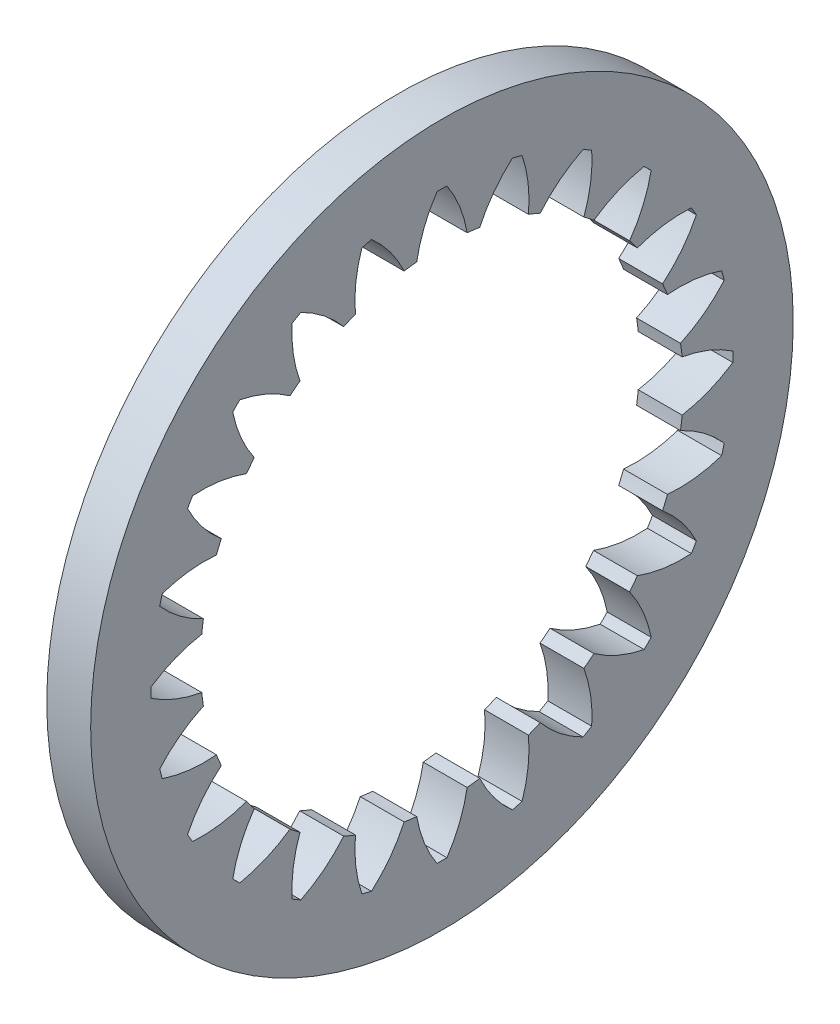
SolidWorks part; units mm, degrees
ref_plane "Plane1" through (0, 0, 0) normal (0, 0, 1) x (1, 0, 0)
ref_plane "Plane2" through (0, 0, 0) normal (0, 1, 0) x (1, 0, 0)
ref_plane "Plane3" through (0, 0, 0) normal (1, 0, 0) x (0, 0, -1)
sketch "HoldingSke" plane through (0, 0, 0) normal (0, 1, 0) x (1, 0, 0)
  line L0 (0, 0) -> (-17.6427, -100.0565)
  line L1 (-15, 0) -> (100, 0) construction
  line L2 (0, 0) -> (-2.1039, 2.3779)
  line L3 (0, 0) -> (-11.863, 4.5341)
  line L4 (0, 0) -> (7.8894, 3.5126)
  line L5 (0, 0) -> (-23.7986, -8.8762)
  line L6 (0, 0) -> (-10.5278, -7.1032)
  line L7 (-2.1039, 2.3779) -> (3.3635, 27.1825)
  line L8 (-76.2, 54.61) -> (-54.61, 54.61)
  line L9 (-67.7845, 28.3722) -> (-49.3413, 33.142)
  line L10 (-76.2, 71.12) -> (104.1128, 71.12)
  line L11 (0, 0) -> (-12.7, 0)
  line L12 (-76.2, 101.6) -> (-75.9714, 101.6)
  line L13 (24.9733, 27.94) -> (52.9518, 28.4284)
  line L14 (24.9733, 27.94) -> (24.9746, 27.94)
  line L15 (24.9733, 27.94) -> (100.4006, 29.5858)
  circle A0 centre (0, 0) radius 101.6
  circle A1 centre (0, 0) radius 12.7
  circle A2 centre (0, 0) radius 12.7
  dimension "Num_teeth" = 24
  dimension "Pitch_radius" = 180.3128
  dimension "Width" = 12.7
  dimension "Thickness" = 12.7
  dimension "Diameter" = 203.2
sketch "BasProSke" plane through (0, 0, 0) normal (0, 1, 0) x (1, 0, 0)
  line L0 (-10, 0) -> (60, 0) construction
  line L1 (0, 69.85) -> (0, 101.6)
  line L2 (0, 69.85) -> (12.7, 69.85)
  line L3 (12.7, 69.85) -> (12.7, 101.6)
  line L4 (12.7, 101.6) -> (0, 101.6)
  dimension "Thickness" = 12.7
  dimension "Diameter" = 203.2
revolve "Base-Revolve" add sketch "BasProSke" angle 360 about L0
sketch "TooCutSke" plane through (0, 0, 0) normal (1, 0, 0) x (0, 0, -1)
  line L3 (5.5552, 75.9972) -> (5.5552, 53.6633) construction
  line L4 (0, 0) -> (0, 59.563) construction
  line L5 (0, 0) -> (-8.9185, 67.7429) construction
  line L6 (-30.2541, 62.9855) -> (28.8527, 70.767) construction
  circle A0 centre (0, 0) radius 76.2 construction
  circle A1 centre (0, 0) radius 84.1388 construction
  circle A2 centre (0, 0) radius 66.3956 construction
  circle A3 centre (0, 0) radius 69.8246 construction
  arc A4 (7.2948, 69.4425) -> (1.4425, 84.1264) centre (-30.2541, 62.9855) ccw
  arc A5 (7.2948, 69.4425) -> (-7.2948, 69.4425) centre (0, 0) ccw
  arc A6 (1.4425, 84.1264) -> (-1.4425, 84.1264) centre (0, 0) ccw
  arc A7 (-1.4425, 84.1264) -> (-7.2948, 69.4425) centre (30.2541, 62.9855) ccw
extrude "ToothCut" cut sketch "TooCutSke" along normal through all
fillet "Breaks" [suppressed] radius 0.635
fillet "RootFillets" [suppressed] radius 1.5888
pattern_circular "TeethCuts" count 24 every 15 about axis through (-10, 0, 0) along (1, 0, 0) of "RootFillets", "Breaks", "ToothCut"
equation "' \"Pitch@HoldingSke\" = 4"
equation "' \"Num_teeth@HoldingSke\" = 24"
equation "' \"Ap@HoldingSke\" =  14.5"
equation "' \"Ap@HoldingSke\" = 14.5"
equation "' \"Width@HoldingSke\" = 0.5"
equation "' \"Diameter@HoldingSke\" = 8"
equation "' \"Show_teeth@HoldingSke\" = 100"
equation "' \"Backlash@HoldingSke\" = 0.009"
equation "' \"Addendum_fac@HoldingSke\" = 1.0"
equation "' \"Dedendum_fac@HoldingSke\" = 1.25"
equation "' \"Dedendum_add@HoldingSke\" = 0.00005"
equation "' \"Clearance_fac@HoldingSke\" = 0.25"
equation "\"Overcut_dia@TooCutSke\" = (\"Num_teeth@HoldingSke\" - 2 * \"Addendum_fac@HoldingSke\") / \"Pitch@HoldingSke\" - 0.002"
equation "\"Pitch_dia@TooCutSke\" = \"Num_teeth@HoldingSke\" / \"Pitch@HoldingSke\""
equation "\"Base_dia@TooCutSke\" = \"Num_teeth@HoldingSke\" / \"Pitch@HoldingSke\" * cos((\"Ap@HoldingSke\"  * 3.14159265 / 180)) * 0.90"
equation "\"Root_dia@TooCutSke\" = \"Num_teeth@HoldingSke\"  / \"Pitch@HoldingSke\" + 2 *  \"Dedendum_fac@HoldingSke\"/ \"Pitch@HoldingSke\" + \"Dedendum_add@HoldingSke\" * 2"
equation "\"Half_ang@TooCutSke\" = 180 / \"Num_teeth@HoldingSke\""
equation "\"Half_CT@TooCutSke\" = \"Num_teeth@HoldingSke\" / \"Pitch@HoldingSke\" * sin((3.14159265 / 2 / \"Num_teeth@HoldingSke\")) / 2 + 10 * \"Backlash@HoldingSke\" / 4"
equation "\"Flank_rad@TooCutSke\" = \"Num_teeth@HoldingSke\" / \"Pitch@HoldingSke\" / 4"
equation "\"Radius@RootFillets\"= \"Clearance_fac@HoldingSke\" / \"Pitch@HoldingSke\" + \"Dedendum_add@HoldingSke\""
equation "\"Break_rad@Breaks\" = 0.02 / \"Pitch@HoldingSke\" * 5"
equation "\"Num_teeth@TeethCuts\" = int( \"Show_teeth@HoldingSke\" ) + 1"
equation "\"Num_teeth@TeethCuts\" = ((sgn( \"Num_teeth@TeethCuts\" - \"Num_teeth@HoldingSke\" )-1)*( \"Num_teeth@TeethCuts\" - \"Num_teeth@HoldingSke\" ))/-2+ \"Num_teeth@HoldingSke\""
equation "\"Num_teeth@TeethCuts\" = ((sgn( \"Num_teeth@TeethCuts\" - 2.0)+1)*( \"Num_teeth@TeethCuts\" - 2.0))/2 +2.0"
equation "\"Angle@TeethCuts\" = 360.0 / \"Num_teeth@HoldingSke\""
equation "\"Diameter@BasProSke\" = \"Num_teeth@HoldingSke\"  / \"Pitch@HoldingSke\" + 2 *  \"Dedendum_fac@HoldingSke\"/ \"Pitch@HoldingSke\" + \"Dedendum_add@HoldingSke\" * 2 + 0.002"
equation "\"Diameter@BasProSke\" = ((sgn( \"Diameter@BasProSke\"  - \"Diameter@HoldingSke\" )+1)*( \"Diameter@BasProSke\"  - \"Diameter@HoldingSke\" ))/2 + \"Diameter@HoldingSke\""
equation "\"Inside_diameter@BasProSke\" =  (\"Num_teeth@HoldingSke\" - 2 * \"Addendum_fac@HoldingSke\") / \"Pitch@HoldingSke\" "
equation "\"Thickness@BasProSke\"  = \"Width@HoldingSke\""
